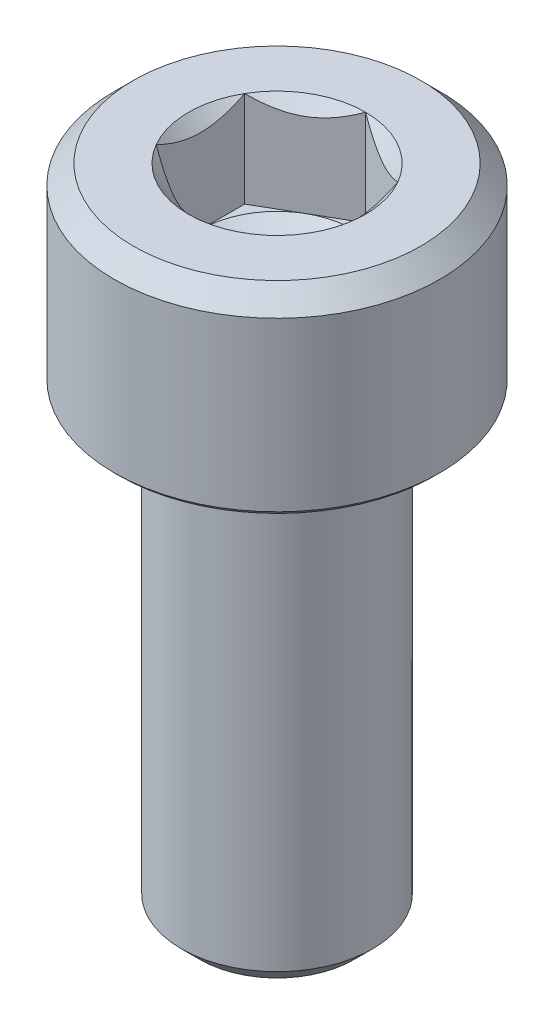
SolidWorks part; units mm, degrees
ref_plane "Front Plane" through (0, 0, 0) normal (0, 0, 1) x (1, 0, 0)
ref_plane "Top Plane" through (0, 0, 0) normal (0, 1, 0) x (1, 0, 0)
ref_plane "Right Plane" through (0, 0, 0) normal (1, 0, 0) x (0, 0, -1)
sketch "Sketch1" plane through (0, 0, 0) normal (0, 0, 1) x (1, 0, 0)
  line L0 (0, 1.3453) -> (2, 2.5)
  line L1 (2, 2.5) -> (2, 4.6906)
  line L2 (2, 4.6906) -> (2.3094, 5)
  line L3 (2.3094, 5) -> (3.75, 5)
  line L4 (3.75, 5) -> (4.25, 4.5)
  line L5 (4.25, 4.5) -> (4.25, 0.125)
  line L6 (4.25, 0.125) -> (4.125, 0)
  line L7 (4.125, 0) -> (2.55, 0)
  line L8 (2.55, 0) -> (2.5, -0.6)
  line L9 (2.5, -0.6) -> (2.5, -11.5095)
  line L10 (2.5, -11.5095) -> (2.0095, -12)
  line L11 (2.0095, -12) -> (0, -12)
  line L12 (0, -12) -> (0, 1.3453)
  line L13 (0, -12) -> (0, 5) construction
revolve "Revolve1" add sketch "Sketch1" angle 360 about L13 reverse direction yes
cosmetic thread "Cosmetic Thread1" parameters "D1"=9.6, "D2"=4.019
ref_plane "Plane1" through (0, 5, 0) normal (0, 1, 0) x (1, 0, 0)
sketch "Sketch2" plane through (0, 5, 0) normal (0, 1, 0) x (1, 0, 0)
  line L0 (-2, -1.1547) -> (0, -2.3094)
  line L1 (0, -2.3094) -> (2, -1.1547)
  line L2 (2, -1.1547) -> (2, 1.1547)
  line L3 (2, 1.1547) -> (0, 2.3094)
  line L4 (0, 2.3094) -> (-2, 1.1547)
  line L5 (-2, 1.1547) -> (-2, -1.1547)
extrude "Cut-Extrude1" cut sketch "Sketch2" against normal blind 2.5
ref_plane "Plane2" through (0, -12, 0) normal (0, 1, 0) x (1, 0, 0)
ref_plane "ANBAU XY" through (0, 0, 0) normal (0, 1, 0) x (1, 0, 0)
ref_plane "ANBAU XZ" through (0, 0, 0) normal (0, 0, 1) x (1, 0, 0)
ref_plane "ANBAU YZ" through (0, 0, 0) normal (1, 0, 0) x (0, 0, -1)
ref_axis "ANBAU X" through (-80.9, 0, 0) along (1, 0, 0)
ref_axis "ANBAU Y" through (0, 0, 50) along (0, 0, -1)
ref_axis "ANBAU Z" through (0, 50, 0) along (0, -1, 0)
sketch3d "ANBAU"
  point P0 (0, 0, 0)
ref_plane "Schraube XY" through (0, 0, 0) normal (0, 1, 0) x (1, 0, 0)
ref_plane "Schraube XZ" through (0, 0, 0) normal (0, 0, 1) x (1, 0, 0)
ref_plane "Schraube YZ" through (0, 0, 0) normal (1, 0, 0) x (0, 0, -1)
ref_axis "Schraube X" through (-80.9, 0, 0) along (1, 0, 0)
ref_axis "Schraube Y" through (0, 0, 50) along (0, 0, -1)
ref_axis "Schraube Z" through (0, 50, 0) along (0, -1, 0)
sketch3d "Schraube"
  point P0 (0, 0, 0)
ref_plane "insert XY" through (0, 0, 0) normal (0, 1, 0) x (1, 0, 0)
ref_plane "insert XZ" through (0, 0, 0) normal (0, 0, 1) x (1, 0, 0)
ref_plane "insert YZ" through (0, 0, 0) normal (1, 0, 0) x (0, 0, -1)
ref_axis "insert X" through (-80.9, 0, 0) along (1, 0, 0)
ref_axis "insert Y" through (0, 0, 50) along (0, 0, -1)
ref_axis "insert Z" through (0, 50, 0) along (0, -1, 0)
sketch3d "insert"
  point P0 (0, 0, 0)
ref_plane "schrauben_punkt XY" through (0, -12, 0) normal (0, 1, 0) x (1, 0, 0)
ref_plane "schrauben_punkt XZ" through (0, 0, 0) normal (0, 0, 1) x (1, 0, 0)
ref_plane "schrauben_punkt YZ" through (0, 0, 0) normal (1, 0, 0) x (0, 0, -1)
ref_axis "schrauben_punkt X" through (-80.9, -12, 0) along (1, 0, 0)
ref_axis "schrauben_punkt Y" through (0, -12, 50) along (0, 0, -1)
ref_axis "schrauben_punkt Z" through (0, 50, 0) along (0, -1, 0)
sketch3d "schrauben_punkt"
  point P0 (0, -12, 0)
other "Freeze***"
